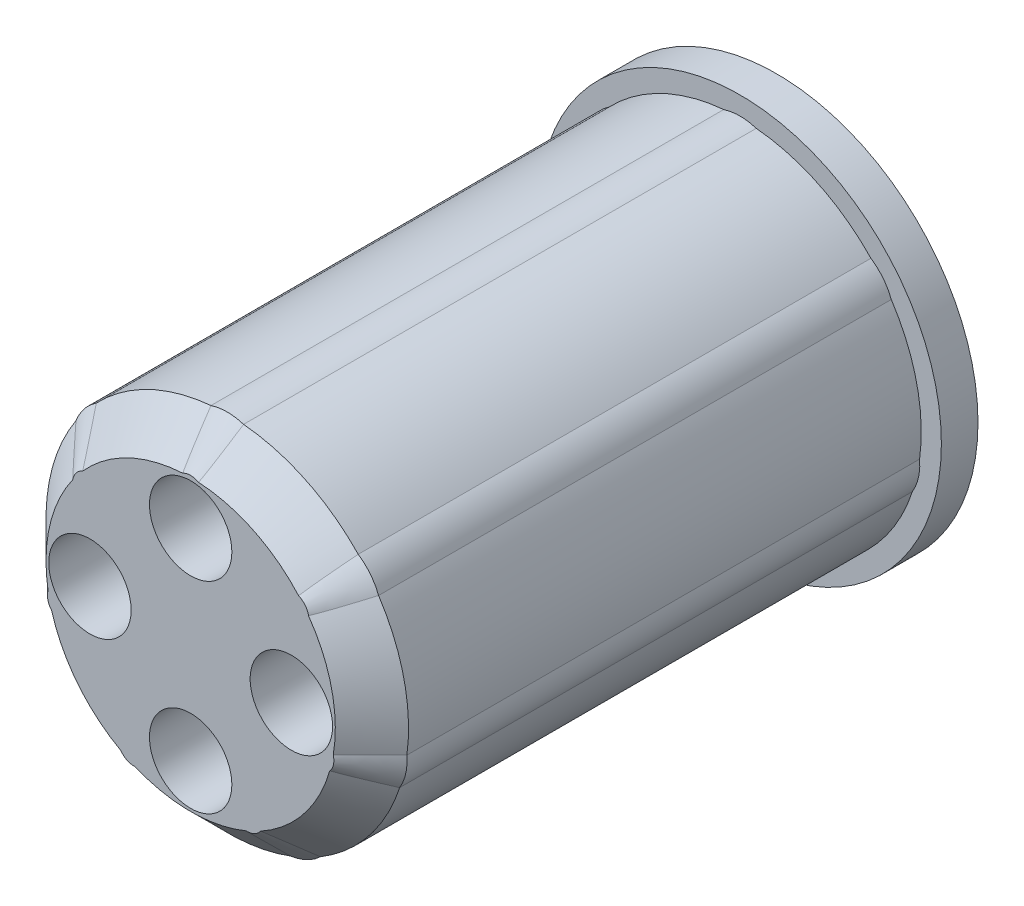
SolidWorks part; units mm, degrees
ref_plane "Ebene vorne" through (0, 0, 0) normal (0, 0, 1) x (1, 0, 0)
ref_plane "Ebene oben" through (0, 0, 0) normal (0, 1, 0) x (1, 0, 0)
ref_plane "Ebene rechts" through (0, 0, 0) normal (1, 0, 0) x (0, 0, -1)
sketch "Skizze1" plane through (0, 0, 0) normal (0, 0, 1) x (1, 0, 0)
  line L0 (0, 0) -> (0, 7.1) construction
  circle A0 centre (0, 0) radius 9.9
  circle A1 centre (0, 0) radius 10 construction
  circle A2 centre (0, 7.1) radius 2.9
  circle A7 centre (5.551, 4.4268) radius 2.9
  circle A8 centre (6.922, -1.5799) radius 2.9
  circle A9 centre (3.0806, -6.3969) radius 2.9
  circle A10 centre (-3.0806, -6.3969) radius 2.9
  circle A11 centre (-6.922, -1.5799) radius 2.9
  circle A12 centre (-5.551, 4.4268) radius 2.9
  point P17 (0, 0)
  point P21 (0, 0)
  dimension "D1" = 19.8
  dimension "D2" = 20
  dimension "D3" = 5.8
  dimension "D4" = 7
extrude "Aufsatz-Linear austragen1" add sketch "Skizze1" along normal blind 32 contours A0 A12 | A0 A2 | A0 A7 | A0 A8 | A0 A9 | A0 A10 | A0 A11 | A0 A11 | A0 A12 | A0 A2 | A0 A8 | A0 A9 | A0 A10 | A12 A0 A11 A10 A9 A8 A7 A2 | A0 A7 region at (0, 0, 0) region at (5.5409, 4.4188, 0) region at (7.7652, 6.1925, 0) region at (9.683, -2.2101, 0) region at (6.9094, -1.577, 0) region at (0, 7.0871, 0) region at (0, 9.932, 0) region at (4.3093, -8.9485, 0) region at (3.075, -6.3853, 0) region at (-5.5409, 4.4188, 0) region at (-7.7652, 6.1925, 0) region at (-4.3093, -8.9485, 0) region at (-3.075, -6.3853, 0) region at (-6.9094, -1.577, 0) region at (-9.683, -2.2101, 0)
sketch "Skizze2" plane through (0, 0, 0) normal (0, 0, 1) x (1, 0, 0)
  circle A0 centre (0, 0) radius 11
  dimension "D1" = 22
extrude "Aufsatz-Linear austragen2" add sketch "Skizze2" along normal blind 2
chamfer "Fase1" distance 2 angle 45 14 edges at (9.7493, -2.2252, 32) (7.7401, -6.1725, 32) (4.3388, -9.0097, 32) (0, -9.9, 32) (-4.3388, -9.0097, 32) (-7.7401, -6.1725, 32) (-9.7493, -2.2252, 32) (-9.6518, 2.203, 32) (-7.8183, 6.2349, 32) (-4.2954, 8.9196, 32) (0, 10, 32) (4.2954, 8.9196, 32) (7.8183, 6.2349, 32) (9.6518, 2.203, 32)
sketch "Skizze3" plane through (0, 0, 2) normal (0, 0, 1) x (1, 0, 0)
  line L0 (0, 0) -> (0, 5.5) construction
  circle A0 centre (0, 0) radius 5.5 construction
  circle A1 centre (0, 5.5) radius 2.25
  circle A2 centre (5.5, 0) radius 2.25
  circle A3 centre (0, -5.5) radius 2.25
  circle A4 centre (-5.5, 0) radius 2.25
  point P14 (0, 0)
  dimension "D1" = 5.5
  dimension "D2" = 4.5
  dimension "D3" = 4
extrude "Schnitt-Linear austragen1" cut sketch "Skizze3" against normal through all and the other way through all
sketch "Skizze4" plane through (0, 0, 0) normal (1, 0, 0) x (0, 0, -1)
  line L0 (-2, 10) -> (-30, 10) construction
  line L1 (-29.7861, 10) -> (-28.4861, 10)
  line L2 (-29.7861, 10) -> (-29.7861, 9.5) construction
  line L3 (-29.7861, 9.5) -> (-28.4861, 9.5)
  line L4 (-28.4861, 10) -> (-28.4861, 9.5)
  line L5 (-29.7861, 9.5) -> (-31.6522, 10)
  line L6 (0, 0) -> (3.3435, 0) construction
  line L8 (-28.1861, 13.3) -> (-28.1861, -13.3) construction
  line L10 (-31.6522, 10) -> (-29.7861, 10)
  dimension "D1" = 0.3
  dimension "D2" = 19
  dimension "D3" = 1.3
  dimension "D4" = 75
revolve "Schnitt-Rotation1" [suppressed] cut sketch "Skizze4" angle 360 about L6
ref_axis "Achse1" through (0, 0, -1.5) along (0, 0, 1)
